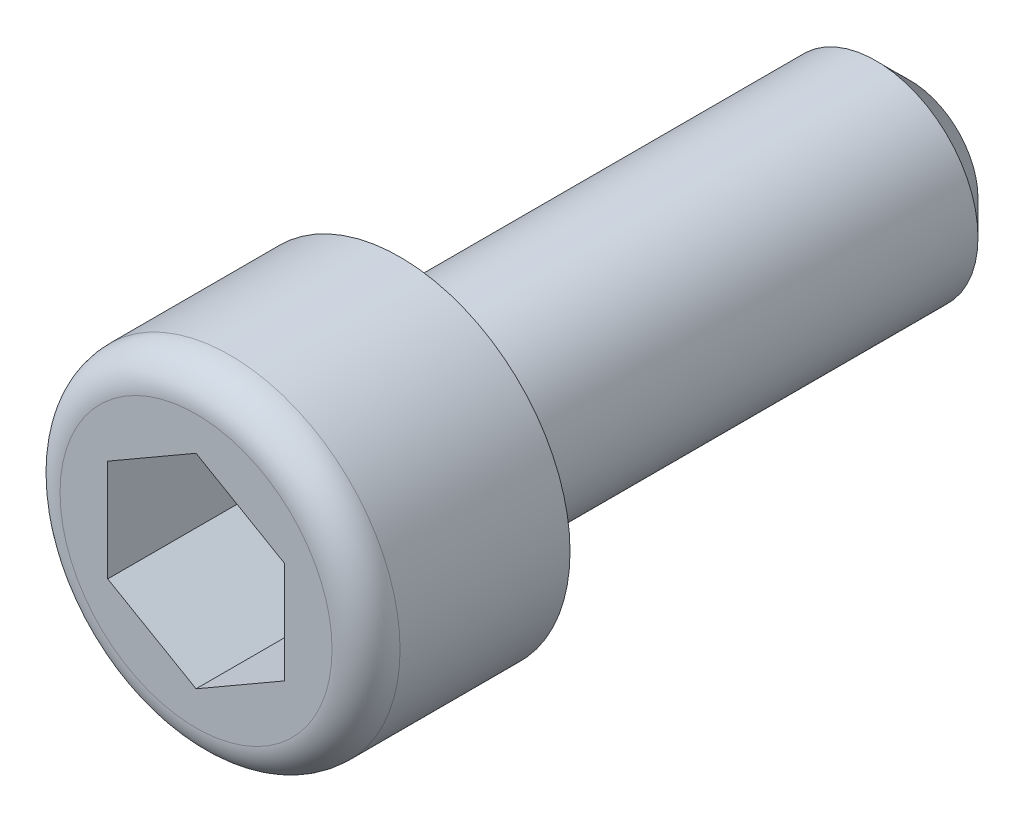
SolidWorks part; units mm, degrees
ref_plane "Front Plane" through (0, 0, 0) normal (0, 0, 1) x (1, 0, 0)
ref_plane "Top Plane" through (0, 0, 0) normal (0, 1, 0) x (1, 0, 0)
ref_plane "Right Plane" through (0, 0, 0) normal (1, 0, 0) x (0, 0, -1)
sketch "Sketch1" plane through (0, 0, 0) normal (1, 0, 0) x (0, 0, -1)
  line L0 (-156.2916, 0) -> (7658.2872, 0) construction
  line L1 (0, 0) -> (0, 5)
  line L2 (0, 5) -> (6, 5)
  line L3 (6, 5) -> (6, 3)
  line L4 (6, 3) -> (21, 3)
  line L5 (21, 3) -> (21, 0)
  line L6 (21, 0) -> (0, 0)
  dimension "D1" = 6
  dimension "D2" = 15
  dimension "D3" = 6
  dimension "D4" = 10
revolve "Body" add sketch "Sketch1" angle 360 about L0
sketch "Sketch2" plane through (0, 0, 0) normal (0, 0, 1) x (1, 0, 0)
  line L1 (0, 3) -> (-2.5981, 1.5)
  line L2 (-2.5981, 1.5) -> (-2.5981, -1.5)
  line L3 (-2.5981, -1.5) -> (0, -3)
  line L4 (0, -3) -> (2.5981, -1.5)
  line L5 (2.5981, -1.5) -> (2.5981, 1.5)
  line L6 (2.5981, 1.5) -> (0, 3)
  circle A0 centre (0, 0) radius 3 construction
  point P1 (0, 0)
  dimension "D1" = 6
extrude "Footprint" cut sketch "Sketch2" against normal blind 4.5
chamfer "Chamfer1" distance 1 angle 45 1 edges at (3, 0, -21)
fillet "Fillet1" radius 1 1 edges at (5, 0, 0)
